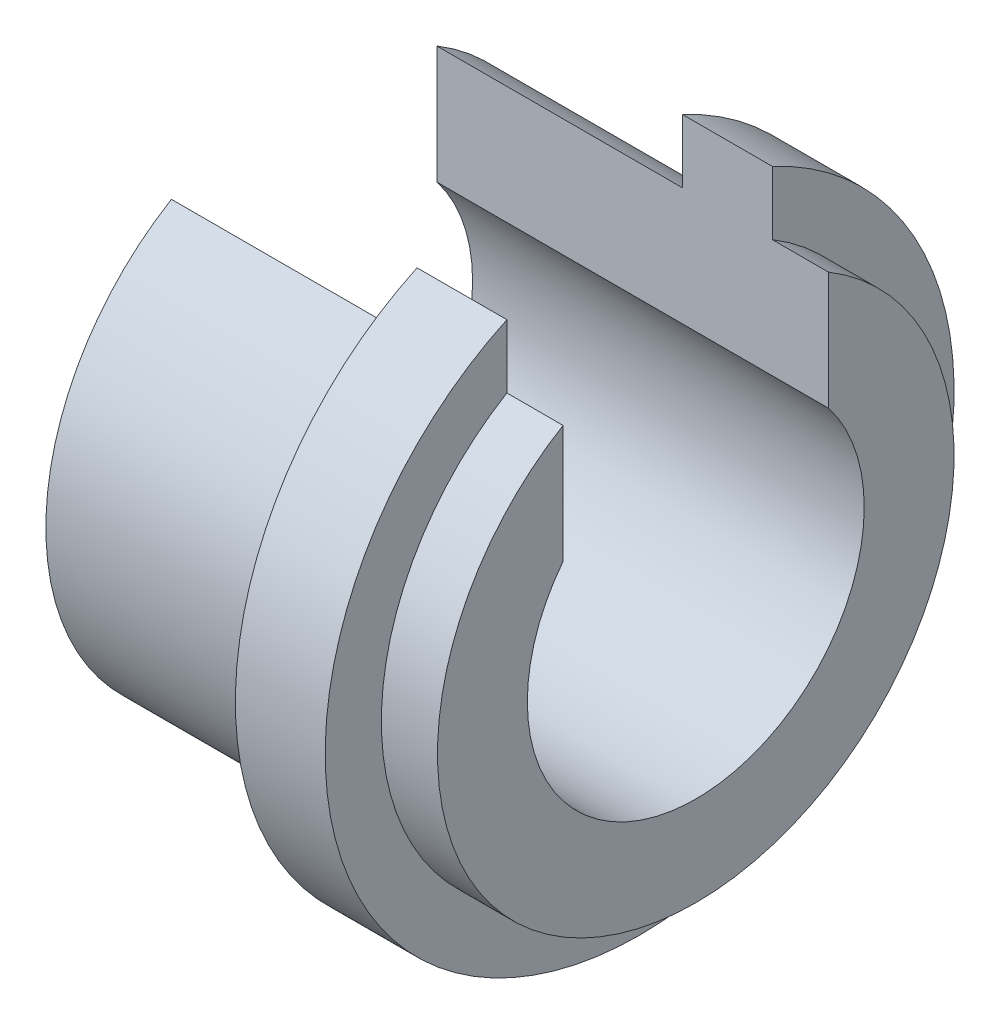
SolidWorks part; units mm, degrees
material "6061-T6 (SS)"
ref_plane "Front Plane" through (0, 0, 0) normal (0, 0, 1) x (1, 0, 0)
ref_plane "Top Plane" through (0, 0, 0) normal (0, 1, 0) x (1, 0, 0)
ref_plane "Right Plane" through (0, 0, 0) normal (1, 0, 0) x (0, 0, -1)
sketch "Sketch1" plane through (0, 0, 0) normal (0, 0, 1) x (1, 0, 0)
  line L0 (0, 0) -> (-16.6687, 0) construction
  line L1 (0, 4.7625) -> (0, 7.3025)
  line L2 (0, 7.3025) -> (-1.5875, 7.3025)
  line L3 (-1.5875, 7.3025) -> (-1.5875, 8.89)
  line L4 (-1.5875, 8.89) -> (-4.1275, 8.89)
  line L5 (-4.1275, 8.89) -> (-4.1275, 7.3025)
  line L6 (-4.1275, 7.3025) -> (-11.0728, 7.3025)
  line L7 (-11.0728, 7.3025) -> (-11.0728, 4.7625)
  line L8 (-11.0728, 4.7625) -> (0, 4.7625)
  dimension "D1" = 9.525
  dimension "D2" = 6.9453
  dimension "D3" = 1.5875
  dimension "D4" = 2.54
revolve "Revolve1" add sketch "Sketch1" angle 360 about L0
sketch "Sketch2" plane through (0, 0, 0) normal (1, 0, 0) x (0, 0, -1)
  line L0 (-3.7531, 2.9319) -> (-3.7531, 8.0589)
  line L1 (3.7531, 8.0589) -> (3.7531, 2.9319)
  circle A0 centre (0, 0) radius 4.7625 construction
  circle A1 centre (0, 0) radius 8.89 construction
  arc A2 (-3.7531, 2.9319) -> (3.7531, 2.9319) centre (0, 0) cw
  arc A3 (-3.7531, 8.0589) -> (3.7531, 8.0589) centre (0, 0) cw
  arc A4 (-3.7531, 4.7229) -> (3.7531, 4.7229) centre (0, 0) cw construction
  circle A5 centre (0, 6.0325) radius 1.27 construction
  circle A6 centre (-2.4831, 5.4978) radius 1.27 construction
  circle A7 centre (2.4831, 5.4978) radius 1.27 construction
  dimension "D1" = 1.27
  dimension "D2" = 2.54
extrude "Cut-Extrude1" cut sketch "Sketch2" against normal through all both
equation "\"bearing1\"=0.273438"
